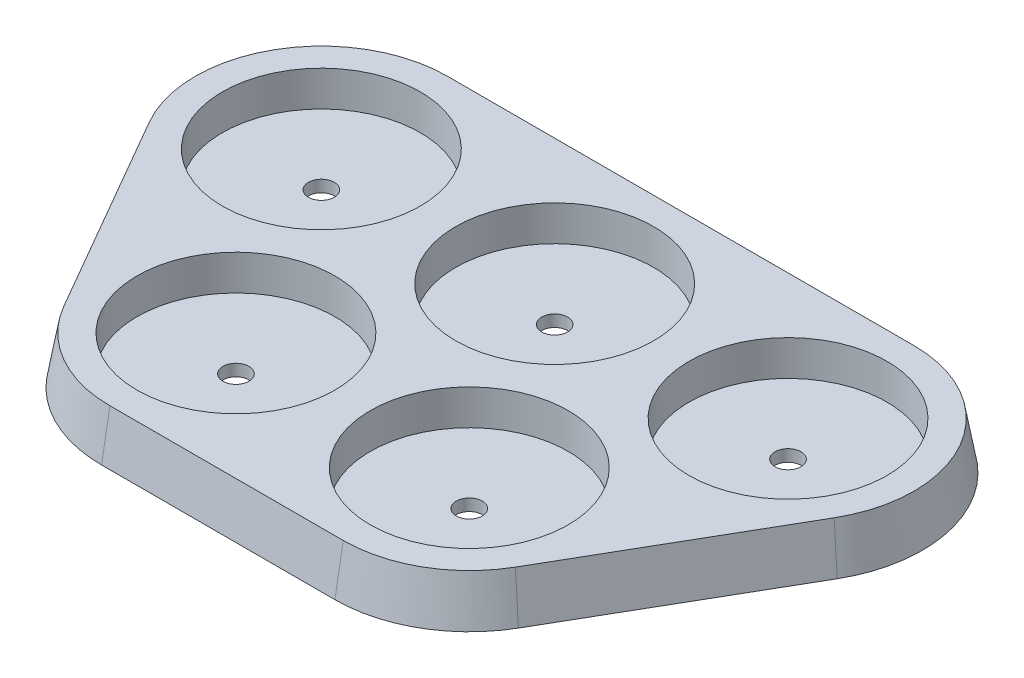
SolidWorks part; units mm, degrees
note: The reader was unsure of these and kept them because the rebuilt part matched: shared geometry of "Sketch1<3>", "Sketch1<4>".
ref_plane "Front Plane" through (0, 0, 0) normal (0, 0, 1) x (1, 0, 0)
ref_plane "Top Plane" through (0, 0, 0) normal (0, 1, 0) x (1, 0, 0)
ref_plane "Right Plane" through (0, 0, 0) normal (1, 0, 0) x (0, 0, -1)
sketch "Sketch1" plane through (0, 0, 0) normal (0, 1, 0) x (1, 0, 0)
  line L0 (0, 0) -> (-9.9, -17.1473) construction
  line L1 (-9.9, -17.1473) -> (-19.8, 0) construction
  line L2 (-19.8, 0) -> (0, 0) construction
  line L3 (9.8727, -5.7) -> (-0.0273, -22.8473)
  line L4 (-9.9, -28.5473) -> (-29.7, -28.5473)
  line L5 (0, 11.4) -> (-19.8, 11.4)
  line L6 (-9.9, -17.1473) -> (-29.7, -17.1473) construction
  line L7 (-29.7, -17.1473) -> (-19.8, 0) construction
  line L8 (-19.8, 11.4) -> (-39.6, 11.4)
  line L9 (-39.5727, -22.8473) -> (-49.4727, -5.7)
  line L10 (-19.8, 0) -> (-39.6, 0) construction
  line L11 (-39.6, 0) -> (-29.7, -17.1473) construction
  circle A0 centre (0, 0) radius 8.4
  circle A1 centre (-19.8, 0) radius 8.4
  circle A2 centre (-9.9, -17.1473) radius 8.4
  circle A3 centre (-9.9, -17.1473) radius 1.1
  circle A4 centre (-19.8, 0) radius 1.1
  circle A5 centre (0, 0) radius 1.1
  circle A6 centre (-9.9, -17.1473) radius 11.4
  circle A7 centre (-19.8, 0) radius 11.4
  circle A8 centre (0, 0) radius 11.4
  circle A9 centre (-29.7, -17.1473) radius 1.1
  circle A10 centre (-29.7, -17.1473) radius 8.4
  circle A11 centre (-29.7, -17.1473) radius 11.4
  circle A12 centre (-39.6, 0) radius 1.1
  circle A13 centre (-39.6, 0) radius 8.4
  circle A14 centre (-39.6, 0) radius 11.4
  point P24 (0, 0)
  dimension "D1" = 16.8
  dimension "D4" = 16.8
  dimension "D5" = 16.8
  dimension "D7" = 2.2
  dimension "D8" = 2.2
  dimension "D9" = 2.2
  dimension "D10" = 22.8
  dimension "D11" = 22.8
  dimension "D12" = 22.8
  dimension "D14" = 2.2
  dimension "D15" = 16.8
  dimension "D16" = 22.8
  dimension "D18" = 16.8
  dimension "D19" = 22.8
  dimension "D20" = 2.2
  dimension "D2" = 60
  dimension "D3" = 60
  dimension "D6" = 19.8
  dimension "D13" = 60
  dimension "D17" = 60
  dimension "D21" = 60
extrude "Boss-Extrude1" add sketch "Sketch1" along normal blind 4 draft 10
extrude "Cut-Extrude1" cut sketch "Sketch1<3>" against normal blind 4 from surface at 4 contours A3 | A5 | A9 | A12 | A4 starting at face at (-19.8, 4, 10.8891)
sketch "Sketch1<3>" plane through (0, 0, 0) normal (0, 1, 0) x (1, 0, 0) same geometry as "Sketch1"
extrude "Cut-Extrude2" cut sketch "Sketch1<4>" against normal blind 3 from surface at 4 contours A1 A4 | A2 A3 | A0 A5 | A10 A9 | A13 A12 starting at face at (0, 4, 1.1)
sketch "Sketch1<4>" plane through (0, 0, 0) normal (0, 1, 0) x (1, 0, 0) same geometry as "Sketch1"
